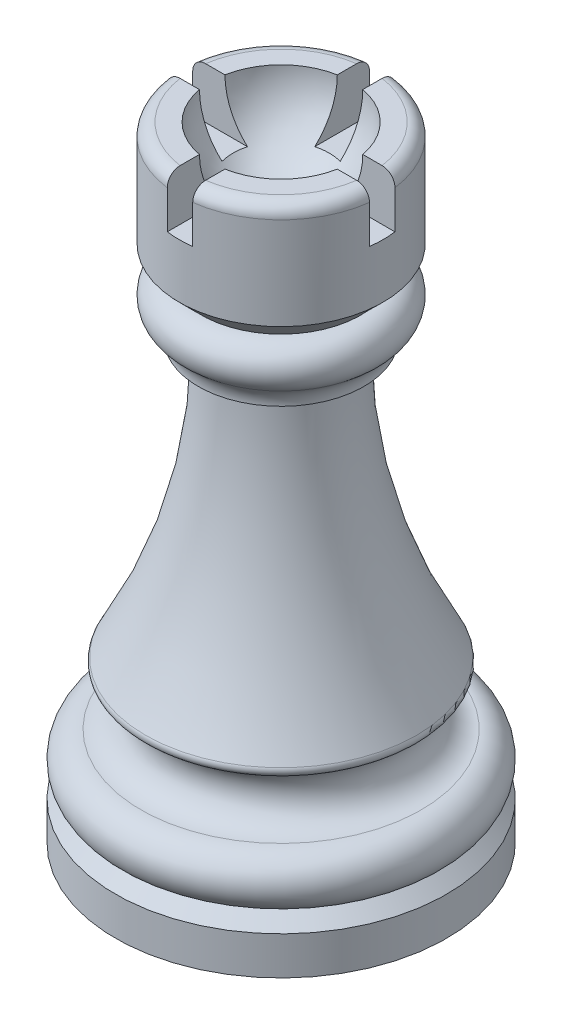
SolidWorks part; units mm, degrees
ref_plane "Front Plane" through (0, 0, 0) normal (0, 0, 1) x (1, 0, 0)
ref_plane "Top Plane" through (0, 0, 0) normal (0, 1, 0) x (1, 0, 0)
ref_plane "Right Plane" through (0, 0, 0) normal (1, 0, 0) x (0, 0, -1)
sketch "Sketch1" plane through (0, 0, 0) normal (1, 0, 0) x (0, 0, -1)
  line L0 (0, 0) -> (0, 43.5)
  line L1 (0, 0) -> (13, 0)
  line L2 (13, 0) -> (13, 3)
  line L3 (13, 3) -> (12, 4)
  line L4 (5, 34) -> (6.5, 34.2645)
  line L5 (5, 34) -> (0, 34) construction
  line L6 (6.2597, 39) -> (8, 40.7403)
  line L7 (8, 40.7403) -> (8, 48)
  line L8 (7, 49) -> (5.5, 49)
  arc A0 (12, 4) -> (11, 7.7321) centre (11, 5.7321) ccw
  arc A1 (11, 12) -> (11, 7.7321) centre (11, 9.866) ccw
  arc A2 (5, 34) -> (11, 12) centre (48.3333, 34) ccw
  arc A3 (7.3021, 35.866) -> (6.5, 34.2645) centre (8.5, 34.2645) ccw
  arc A4 (7.3021, 35.866) -> (6.2597, 39) centre (6.2597, 37.2597) ccw
  arc A5 (8, 48) -> (7, 49) centre (7, 48) ccw
  arc A6 (0, 43.5) -> (5.5, 49) centre (0, 49) ccw
  point P7 (6.5, 34.2645)
  point P10 (0, 12)
  point P11 (11, 12)
  point P12 (5, 34)
  point P24 (7.3021, 35.866)
  point P25 (8, 37.2597)
  point P26 (6.2597, 39)
  dimension "D6" = 4
  dimension "D15" = 2
  dimension "D16" = 4
  dimension "D17" = 1.5
  dimension "D18" = 5.5
  dimension "D1" = 49
  dimension "D2" = 13
  dimension "D3" = 3
  dimension "D4" = 1
  dimension "D5" = 45
  dimension "D7" = 12
  dimension "D8" = 5
  dimension "D9" = 34
  dimension "D10" = 6.5
  dimension "D11" = 10
  dimension "D12" = 8
  dimension "D13" = 39
  dimension "D14" = 45
  dimension "D19" = 43.5
revolve "Revolve2" add sketch "Sketch1" angle 360 about L0
fillet "Fillet1" radius 0.5 1 edges at (0, 12, -11)
sketch "Sketch2" plane through (0, 0, 0) normal (1, 0, 0) x (0, 0, -1)
  line L0 (5.5, 49) -> (-5.5, 49) construction
  line L1 (-1, 49) -> (1, 49)
  line L2 (-1, 49) -> (-1, 45)
  line L3 (-1, 45) -> (1, 45)
  line L4 (1, 49) -> (1, 45)
  line L5 (0, 49) -> (0, 51.7203) construction
  dimension "D1" = 4
  dimension "D2" = 2
extrude "Cut-Extrude1" cut sketch "Sketch2" against normal blind 10 and the other way blind 10
sketch "Sketch3" plane through (0, 0, 0) normal (0, 0, 1) x (1, 0, 0)
  line L0 (0, 0) -> (0, 4) construction
  line L1 (6.9282, 49) -> (-6.9282, 49) construction
  line L2 (-1, 49) -> (1, 49)
  line L3 (-1, 49) -> (-1, 45)
  line L4 (-1, 45) -> (1, 45)
  line L5 (1, 49) -> (1, 45)
  dimension "D1" = 4
  dimension "D2" = 2
extrude "Cut-Extrude2" cut sketch "Sketch3" against normal blind 10 and the other way blind 10
